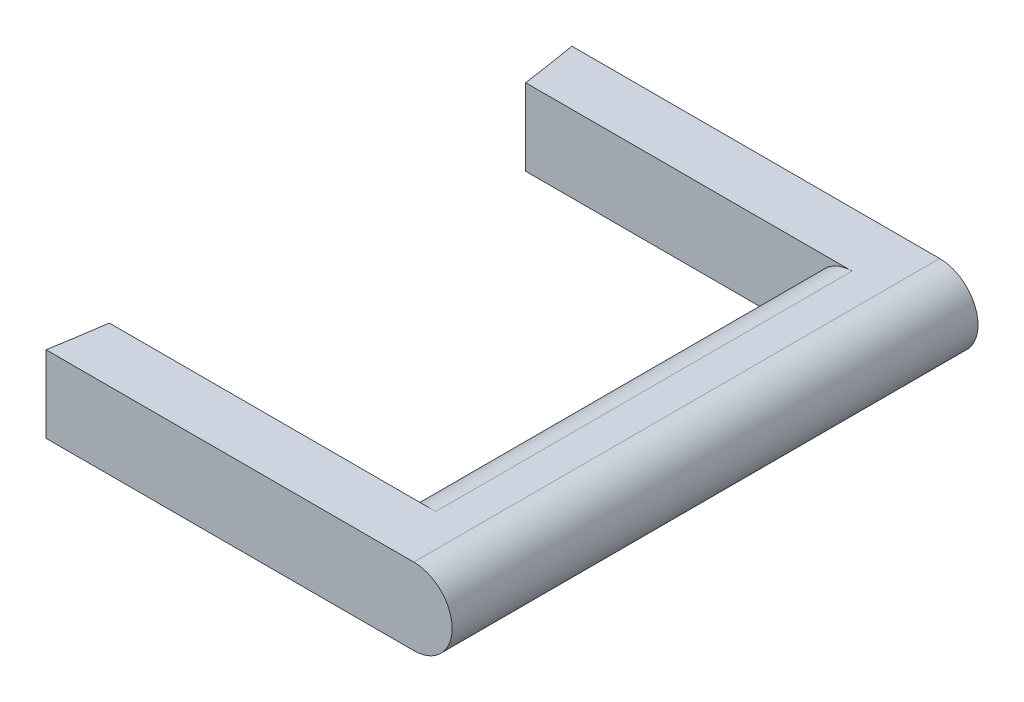
SolidWorks part; units mm, degrees
material "6061-T6 (SS)"
ref_plane "Front" through (0, 0, 0) normal (0, 0, 1) x (1, 0, 0)
ref_plane "Top" through (0, 0, 0) normal (0, 1, 0) x (1, 0, 0)
ref_plane "Right" through (0, 0, 0) normal (1, 0, 0) x (0, 0, -1)
sketch "Sketch1" plane through (0, 0, 0) normal (0, 1, 0) x (1, 0, 0)
  line L0 (137.9275, 24) -> (175, 24)
  line L1 (165, 19) -> (138.7047, 19)
  line L2 (165, -19) -> (165, 19)
  line L3 (175, 24) -> (175, -24)
  line L5 (175, -24) -> (137.9275, -24)
  line L6 (165, -19) -> (138.7047, -19)
  arc A0 (137.9275, 24) -> (138.7047, 19) centre (0, 0) cw
  arc A5 (138.7047, -19) -> (137.9275, -24) centre (0, 0) cw
  point P3 (0, 0)
  point P5 (0, 0)
  point P10 (0, 0)
  point P11 (0, 0)
  point P12 (0, 0)
  point P14 (0, 0)
  point P16 (0, 0)
  point P17 (0, 0)
  point P18 (0, 0)
  point P19 (0, 0)
  point P20 (0, 0)
  point P21 (0, 0)
  point P22 (0, 0)
  point P23 (0, 0)
  point P24 (0, 0)
  point P25 (0, 0)
  point P26 (0, 0)
  point P27 (0, 0)
  point P28 (0, 0)
  point P29 (0, 0)
  point P30 (0, 0)
  point P31 (0, 0)
  point P32 (0, 0)
  point P33 (0, 0)
  point P34 (0, 0)
extrude "Boss-Extrude1" add sketch "Sketch1" along normal blind 7 contours L6 A5 L5 L3 L0 A0 L1 L2
fillet "Fillet1" 2 edges at (175, 7, 0) (175, 0, 0) type full round first side face at (154.1637, 7, 0) second side face at (154.1637, 0, 0) middle face at (175, 3.5, 0)
fillet "Fillet2" 2 edges at (165, 7, 0) (165, 0, 0) type full round first side face at (153.2887, 7, 0) second side face at (153.2887, 0, 0) middle face at (165, 3.5, 0)
